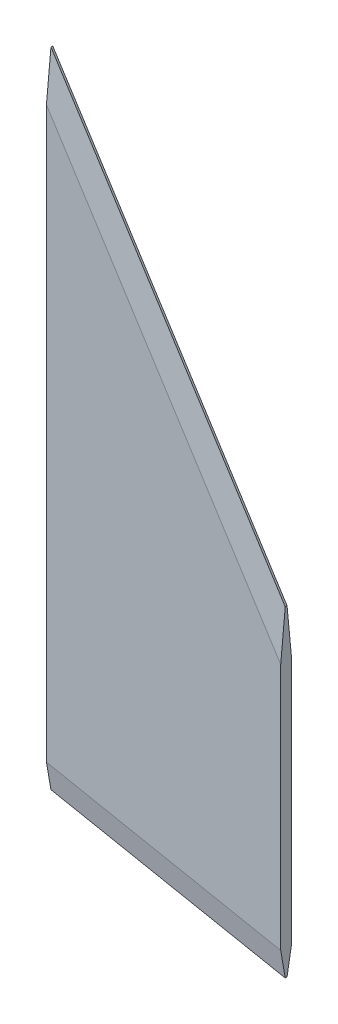
SolidWorks part; units mm, degrees
material "Hexcel AS4C (3000 Filaments)"
ref_plane "Front Plane" through (0, 0, 0) normal (0, 0, 1) x (1, 0, 0)
ref_plane "Top Plane" through (0, 0, 0) normal (0, 1, 0) x (1, 0, 0)
ref_plane "Right Plane" through (0, 0, 0) normal (1, 0, 0) x (0, 0, -1)
sketch "Sketch1" plane through (0, 0, 0) normal (0, 0, 1) x (1, 0, 0)
  line L0 (-60.9816, 86.6315) -> (-60.9816, -91.1685)
  line L1 (-60.9816, -91.1685) -> (3.7884, -103.8685)
  line L2 (3.7884, -103.8685) -> (3.7884, -14.9685)
  line L3 (3.7884, -14.9685) -> (-60.9816, 86.6315)
extrude "Boss-Extrude1" add sketch "Sketch1" along normal mid plane 3
chamfer "Chamfer1" distance 1.25 angle 80 4 edges at (-28.5966, -97.5185, -1.5) (-28.5966, -97.5185, 1.5) (-28.5966, 35.8315, -1.5) (-28.5966, 35.8315, 1.5) first distance on face at (-28.5966, -97.5185, 0) first distance on face at (-28.5966, 35.8315, 0)
